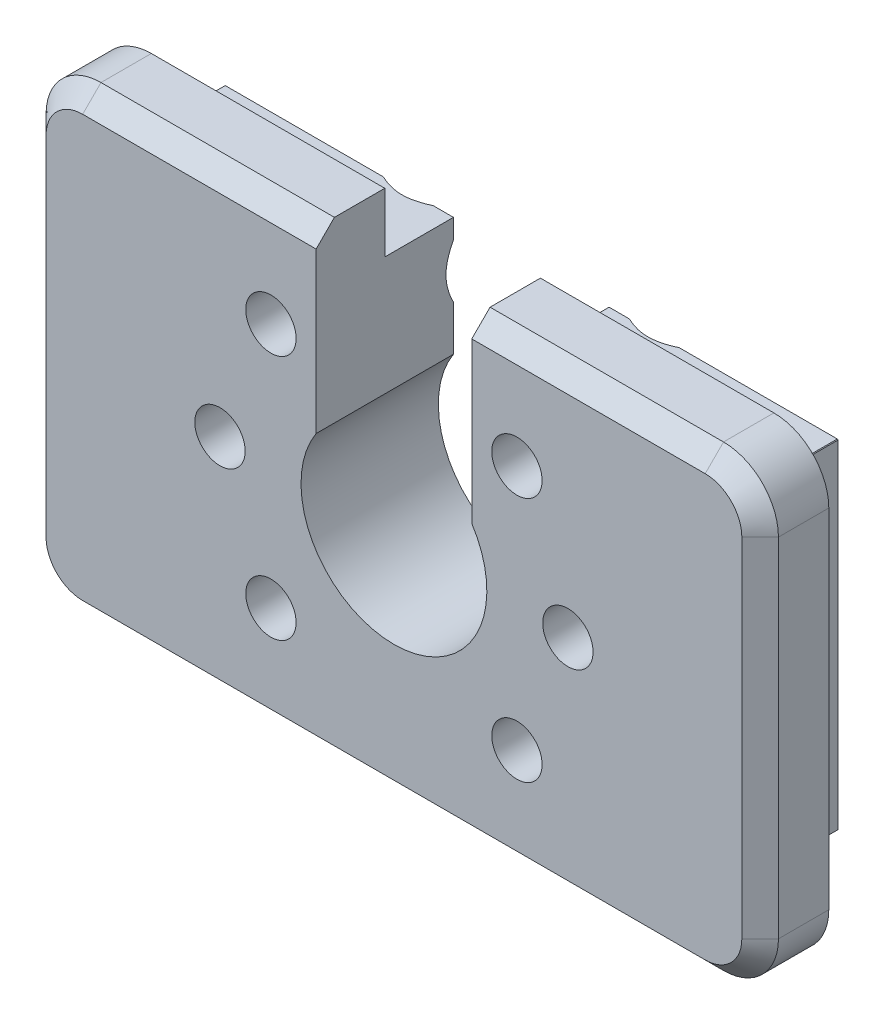
SolidWorks part; units mm, degrees
material "PET"
ref_plane "Front Plane" through (0, 0, 0) normal (0, 0, 1) x (1, 0, 0)
ref_plane "Top Plane" through (0, 0, 0) normal (0, 1, 0) x (1, 0, 0)
ref_plane "Right Plane" through (0, 0, 0) normal (1, 0, 0) x (0, 0, -1)
sketch "Sketch1" plane through (0, 0, 0) normal (0, 0, 1) x (1, 0, 0)
  line L1 (40, -25) -> (-40, -25)
  line L2 (40, -25) -> (40, 25)
  line L3 (40, 25) -> (-40, 25)
  line L4 (-40, -25) -> (-40, 25)
  line L5 (40, -25) -> (-40, 25) construction
  line L6 (40, 25) -> (-40, -25) construction
  point P0 (0, 0)
  dimension "D1" = 50
  dimension "D2" = 80
extrude "Boss-Extrude1" add sketch "Sketch1" against normal blind 7.5
sketch "Sketch2" plane through (0, 0, -7.5) normal (0, 0, -1) x (-1, 0, 0)
  line L8 (33.5, -18.5) -> (33.5, 18.5)
  line L9 (33.5, 18.5) -> (-33.5, 18.5)
  line L10 (-33.5, 18.5) -> (-33.5, -18.5)
  line L11 (-33.5, -18.5) -> (33.5, -18.5)
  line L12 (33.5, -18.5) -> (33.5, 18.5)
  line L13 (33.5, 18.5) -> (-33.5, 18.5)
  line L14 (-33.5, 18.5) -> (-33.5, -18.5)
  line L15 (-33.5, -18.5) -> (33.5, -18.5)
  dimension "D1" = 6.5
extrude "Boss-Extrude2" add sketch "Sketch2" along normal blind 7.5
sketch "Sketch3" plane through (0, 0, 0) normal (0, 0, 1) x (1, 0, 0)
  line L0 (0, 0) -> (0, 51.1675) construction
  line L1 (40, 25) -> (-40, 25) construction
  line L2 (8.5, 5.5473) -> (-8.5, 5.5473) construction
  line L3 (8.5, 5.5473) -> (8.5, 25)
  line L4 (8.5, 25) -> (-8.5, 25)
  line L5 (-8.5, 5.5473) -> (-8.5, 25)
  line L6 (8.5, 5.5473) -> (-8.5, 25) construction
  line L7 (8.5, 25) -> (-8.5, 5.5473) construction
  line L8 (0, 0) -> (-19, 0) construction
  arc A0 (-8.5, 5.5473) -> (8.5, 5.5473) centre (0, 0) ccw
  circle A1 centre (-19, 0) radius 2.75
  circle A2 centre (-13.435, 13.435) radius 2.75
  circle A3 centre (0, 19) radius 2.75 construction
  circle A4 centre (13.435, 13.435) radius 2.75
  circle A5 centre (19, 0) radius 2.75
  circle A6 centre (13.435, -13.435) radius 2.75
  circle A7 centre (0, -19) radius 2.75 construction
  circle A8 centre (-13.435, -13.435) radius 2.75
  point P3 (0, 15.2736)
  point P28 (0, 0)
  dimension "D4" = 5.5
  dimension "D2" = 17
  dimension "D3" = 19
  dimension "D5" = 8
extrude "Cut-Extrude1" cut sketch "Sketch3" against normal through all
fillet "Fillet1" radius 6 4 edges at (40, -25, -3.75) (-40, -25, -3.75) (-40, 25, -3.75) (40, 25, -3.75)
sketch "Sketch4" plane through (0, 0, -15) normal (0, 0, -1) x (-1, 0, 0)
  line L0 (-37, 22) -> (-37, -22) construction
  line L1 (-40, -19) -> (-40, 19) construction
  line L2 (-34, 25) -> (-8.5, 25) construction
  line L4 (34, -25) -> (-34, -25) construction
  line L5 (-37, -22) -> (0, -22) construction
  line L6 (0, 0) -> (0, -22) construction
  circle A0 centre (-37, 22) radius 5
  circle A1 centre (-37, -22) radius 5
  circle A2 centre (-37, 0) radius 2.5
  circle A3 centre (0, -22) radius 2.5
  circle A4 centre (37, -22) radius 5
  circle A5 centre (37, 0) radius 2.5
  circle A6 centre (37, 22) radius 5
  dimension "D4" = 5
  dimension "D5" = 10
  dimension "D1" = 3
  dimension "D2" = 3
  dimension "D3" = 3
extrude "Cut-Extrude2" cut sketch "Sketch4" against normal up to surface (7.5 mm away) up to face at (0, 5.4375, -7.5)
chamfer "Chamfer1" distance 2 angle 45 9 edges at (-21.25, 25, 0) (-38.2426, 23.2426, 0) (-40, 0, 0) (-38.2426, -23.2426, 0) (0, -25, 0) (38.2426, -23.2426, 0) (40, 0, 0) (38.2426, 23.2426, 0) (21.25, 25, 0)
chamfer "Chamfer2" distance 3 angle 45 6 edges at (16.185, -13.435, -15) (-16.25, 0, -15) (-10.685, -13.435, -15) (21.75, 0, -15) (16.185, 13.435, -15) (-10.685, 13.435, -15)
equation "\"hole_radius\"= 10.15mm"
equation "\"D1@Sketch3\"=\"hole_radius\"*2"
equation "\"M5_tap\"=4.2mm"
equation "\"M5_clearence\"=5.5mm"
equation "\"M6_tap\"=5mm"
equation "\"M6_clearence\"=6.6mm"
equation "\"work_area_width\"=1100mm"
equation "\"work_area_depth\"=900mm"
equation "\"steel_base_width\"=80mm"
equation "\"steel_base_height\"=50mm"
equation "\"steel_base_wall_thickness\"=3mm"
equation "\"steel_base_radius\"=6mm"
equation "\"steel_sides_width\"=180mm"
equation "\"steel_sides_height\"=50mm"
equation "\"steel_sides_wall_thickness\"=5mm"
equation "\"steel_sides_radius\"=6mm"
equation "\"steel_gantry_width\"=120mm"
equation "\"steel_gantry_height\"=80mm"
equation "\"steel_gantry_wall_thickness\"=6mm"
equation "\"steel_gantry_radius\"=6mm"
equation "\"steel_rollers_width\"=80mm"
equation "\"steel_rollers_height\"=50mm"
equation "\"steel_rollers_wall_thickness\"=6mm"
equation "\"steel_rollers_radius\"=6mm"
equation "\"steel_zbox_width\"=400mm"
equation "\"steel_zbox_height\"=90mm"
equation "\"steel_zbox_wall_thickness\"=3mm"
equation "\"steel_zbox_radius\"=6mm"
equation "\"D2@Sketch1\"=\"steel_rollers_width\""
equation "\"D1@Sketch1\"=\"steel_rollers_height\""
equation "\"D1@Sketch2\"=\"steel_rollers_wall_thickness\" + 0.5mm"
